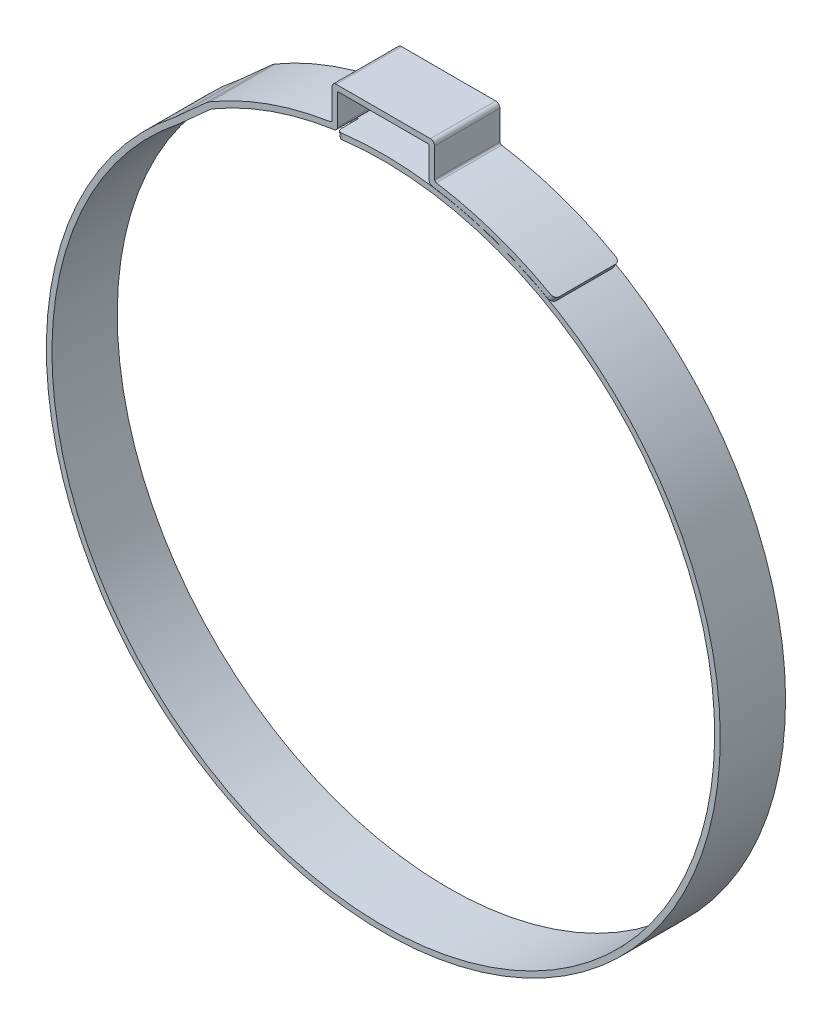
SolidWorks part; units mm, degrees
note: '?' marks a value the reader was unsure of.
material "Alloy Steel"
ref_plane "Front" through (0, 0, 0) normal (0, 0, 1) x (1, 0, 0)
ref_plane "Top" through (0, 0, 0) normal (0, 1, 0) x (1, 0, 0)
ref_plane "Right" through (0, 0, 0) normal (1, 0, 0) x (0, 0, -1)
sketch "Sketch1" plane through (0, 0, 0) normal (0, 0, 1) x (1, 0, 0)
  line L0 (0, 0) -> (0, 36.25) construction
  line L1 (0, 36.25) -> (0, 40.2945) construction
  line L2 (-5, 36.25) -> (5, 36.25) construction
  line L3 (-5, 36.5445) -> (-5, 40.2945) construction
  line L4 (-5, 40.2945) -> (5, 40.2945) construction
  line L5 (5, 40.2945) -> (5, 36.5445) construction
  line L6 (-36.25, 0) -> (0, 0) construction
  line L7 (0, 0) -> (36.25, 0) construction
  line L8 (-5.6096, 36.5445) -> (-5.6096, 40.9041)
  line L9 (-5, 36.5445) -> (-5.6096, 36.5445)
  line L10 (-5.6096, 40.9041) -> (5.6096, 40.9041)
  line L11 (5.6096, 40.9041) -> (5.6096, 36.5445)
  line L12 (5.6096, 36.5445) -> (5, 36.5445)
  line L13 (0, 40.2945) -> (0, 40.9041) construction
  line L14 (-5, 36.5445) -> (5, 36.5445)
  circle A0 centre (0, 0) radius 36.25 construction
  circle A1 centre (0, 0) radius 36.8596 construction
  circle A2 centre (0, 0) radius 36.885 construction
  dimension "D3" = 3.75
  dimension "D1" = 0.6096
extrude "Boss-Extrude1" add sketch "Sketch1" along normal mid plane 7.1437
sketch "Sketch4" plane through (0, 40.9041, 0) normal (0, 1, 0) x (1, 0, 0)
  line L0 (-1.9284, 0) -> (-3, 0) construction
  line L1 (0, -1.0716) -> (0, 1.0716) construction
  line L2 (-1.9284, 0) -> (1.9284, 0) construction
  line L3 (-36.25, 0) -> (36.25, 0) construction
  line L4 (-1.9284, 1.0716) -> (1.9284, 1.0716)
  line L5 (-1.9284, -1.0716) -> (1.9284, -1.0716)
  line L6 (1.9284, 0) -> (3, 0) construction
  arc A0 (-1.9284, 1.0716) -> (-1.9284, -1.0716) centre (-1.9284, 0) ccw
  arc A1 (1.9284, -1.0716) -> (1.9284, 1.0716) centre (1.9284, 0) ccw
  point P5 (0, 0)
  dimension "D2" = 2.1431
  dimension "D1" = 6
extrude "Cut-Extrude1" [suppressed] cut sketch "Sketch4" against normal blind 0.75
fillet "Fillet1" [suppressed] radius 0.4875
fillet "Fillet2" [suppressed] radius 0.1875
shell "Shell1" thickness 0.6096
sketch "Sketch5" plane through (0, 0, 0) normal (0, 0, 1) x (1, 0, 0)
  line L0 (18.4338, 31.9483) -> (0, 0) construction
  line L1 (5, 36.5445) -> (0, 0) construction
  arc A0 (5, 36.5445) -> (18.4338, 31.9483) centre (0, 0) cw
  dimension "Connector Strap Length" = 14.2875
extrude "Extrude-Thin3" add sketch "Sketch5" along normal mid plane 7.1437 thin thin type one direction reverse wall 0.6096
sketch "Sketch6" plane through (0, 0, 0) normal (0, 0, 1) x (1, 0, 0)
  line L0 (-18.8456, 31.7072) -> (0, 0) construction
  line L2 (-19.0354, 31.5362) -> (-22.3687, 28.5326)
  line L3 (-29.0363, 21.7015) -> (0, 0) construction
  line L4 (-22.4301, 28.4772) -> (0, 0) construction
  arc A0 (-5, 36.5445) -> (-18.6176, 31.8416) centre (0, 0) ccw
  arc A1 (-29.0363, 21.7015) -> (-5, 35.9035) centre (0, 0) ccw
  arc A2 (-22.3687, 28.5326) -> (-22.4929, 28.4277) centre (-24.0674, 30.4176) cw
  arc A3 (-18.6176, 31.8416) -> (-19.0354, 31.5362) centre (-17.3368, 29.6511) ccw
  arc A4 (-29.0363, 21.7015) -> (-22.4929, 28.4277) centre (0, 0) cw
  circle A5 centre (0, 0) radius 36.25 construction
  dimension "D4" = 2.5375
  dimension "D2" = 15
  dimension "D3" = 7.5
  dimension "D1" = 14.5
extrude "Extrude-Thin4" add sketch "Sketch6" along normal mid plane 7.1437 thin
sketch "Sketch7" plane through (0, 0, 0) normal (0, 0, 1) x (1, 0, 0)
  line L1 (-18.9253, 32.3679) -> (-18.6176, 31.8416)
  line L3 (-18.6176, 31.8416) -> (0, 0)
  line L4 (-35.6555, 9.3444) -> (-38.0388, 9.969)
  line L5 (-18.9253, 32.3679) -> (-19.8484, 33.9466)
  line L6 (0, 0) -> (-35.6555, 9.3444)
  arc A0 (-38.0388, 9.969) -> (-19.8484, 33.9466) centre (0, 0) cw
  arc A1 (-18.6176, 31.8416) -> (-19.0354, 31.5362) centre (-17.3368, 29.6511) ccw construction
  arc A2 (-5, 36.5445) -> (-18.6176, 31.8416) centre (0, 0) ccw construction
  arc A10 (-22.8711, 28.9058) -> (-5.0841, 36.5073) centre (0, 0) ccw construction
  dimension "D1" = 1.8288
  dimension "D2" = 45
extrude "Cut-Extrude2" [suppressed] cut sketch "Sketch7" against normal mid plane 2.432
sketch "Sketch8" [suppressed] plane through (0, 0, 0) normal (0, 0, 1) x (1, 0, 0)
  line L0 (-31.3283, 23.7669) -> (0, 0) construction
  line L1 (0, 0) -> (-35.0658, 9.1898) construction
  line L2 (0, 0) -> (-18.6176, 31.8416) construction
  line L3 (-29.3654, 22.2778) -> (-28.8798, 21.9094) construction
  line L4 (-24.4134, 27.4997) -> (0, 0) construction
  line L5 (-32.6967, 15.8784) -> (0, 0) construction
  arc A0 (-5, 36.5445) -> (-18.6176, 31.8416) centre (0, 0) ccw construction
  arc A1 (-5, 36.5445) -> (-18.6176, 31.8416) centre (0, 0) ccw construction
  arc A2 (-19.8484, 33.9466) -> (-38.0388, 9.969) centre (0, 0) ccw construction
  arc A3 (-35.0658, 9.1898) -> (-5, 35.9035) centre (0, 0) ccw construction
  circle A4 centre (0, 0) radius 36.8596 construction
  arc A5 (-22.4929, 28.4277) -> (-5, 35.9035) centre (0, 0) ccw construction
  circle A6 centre (0, 0) radius 36.25 construction
  arc A7 (-35.0658, 9.1898) -> (-32.6967, 15.8784) centre (5.7902, -1.5175) cw
  arc A8 (-32.6967, 15.8784) -> (-24.4134, 27.4997) centre (0.9059, 0.6902) cw
  arc A9 (-24.4134, 27.4997) -> (-18.6176, 31.8416) centre (-2.532, 4.3304) cw
  point P19 (-29.1226, 22.0936)
  dimension "D1" = 22.5
extrude "Extrude-Thin5" [suppressed] add sketch "Sketch8" along normal mid plane 2.3813 thin
sketch "Sketch12" [suppressed] plane through (0, 0, 0) normal (0, 0, 1) x (1, 0, 0)
  line L0 (-5.6453, -0.2315) -> (0, 0) construction
  line L1 (0, 0) -> (-4.5478, 4.1895) construction
  line L2 (-5.5488, 2.0363) -> (0, 0) construction
  arc A0 (-2.75, 5.5382) -> (-4.5478, 4.1895) centre (0, 0) ccw construction
  arc A1 (-2.75, 5.5382) -> (-4.5478, 4.1895) centre (0, 0) ccw construction
  arc A2 (-5.6453, -0.2315) -> (0, -5.65) centre (0, 0) ccw construction
  arc A3 (-5.6453, -0.2315) -> (-5.5488, 2.0363) centre (7.9561, 0.3262) cw
  arc A4 (-5.5488, 2.0363) -> (-4.5478, 4.1895) centre (-1.6784, 1.5462) cw
  dimension "D1" = 22.5
extrude "Extrude-Thin7" [suppressed] add sketch "Sketch12" along normal mid plane 2.3813 thin
sketch "Sketch9" plane through (0, 0, 0) normal (0, 0, 1) x (1, 0, 0)
  line L0 (0, 0) -> (-18.2971, 31.2934) construction
  line L4 (-18.9253, 32.3679) -> (-18.2971, 31.2934) construction
  arc A0 (-5, 35.9035) -> (-18.2971, 31.2934) centre (0, 0) ccw
  circle A1 centre (0, 0) radius 36.25 construction
extrude "Extrude-Thin6" add sketch "Sketch9" along normal mid plane 2.3813 thin
sketch "Sketch10" plane through (0, 0, 0) normal (0, 0, 1) x (1, 0, 0)
  line L0 (0, 0) -> (16.4971, 33.6703) construction
  line L1 (0, 0) -> (15.3474, 34.2097) construction
  line L2 (0, 0) -> (14.1801, 34.7098) construction
  line L3 (0, 0) -> (12.9965, 35.1701) construction
  line L4 (0, 0) -> (18.7385, 32.4764) construction
  line L5 (0, 0) -> (11.798, 35.59) construction
  line L6 (0, 0) -> (10.586, 35.9692) construction
  line L7 (10.586, 35.9692) -> (10.4067, 35.36)
  line L8 (11.798, 35.59) -> (11.5982, 34.9873)
  line L9 (12.9965, 35.1701) -> (12.7764, 34.5745)
  line L10 (14.1801, 34.7098) -> (13.94, 34.1219)
  line L11 (15.3474, 34.2097) -> (15.0875, 33.6303)
  line L12 (16.4971, 33.6703) -> (16.2178, 33.1001)
  arc A0 (18.7385, 32.4764) -> (5.6096, 37.0726) centre (0, 0) ccw construction
  arc A1 (10.586, 35.9692) -> (11.798, 35.59) centre (0, 0) cw
  circle A2 centre (0, 0) radius 36.8596 construction
  arc A3 (10.4067, 35.36) -> (11.5982, 34.9873) centre (0, 0) cw
  arc A4 (12.9965, 35.1701) -> (14.1801, 34.7098) centre (0, 0) cw
  arc A5 (15.3474, 34.2097) -> (16.4971, 33.6703) centre (0, 0) cw
  arc A6 (12.7764, 34.5745) -> (13.94, 34.1219) centre (0, 0) cw
  arc A7 (15.0875, 33.6303) -> (16.2178, 33.1001) centre (0, 0) cw
  dimension "D3" = 1.27
  dimension "D4" = 1.27
  dimension "D5" = 1.27
  dimension "D6" = 1.27
extrude "Cut-Extrude3" [suppressed] cut sketch "Sketch10" against normal mid plane 1.7859
fillet "Fillet4" radius 0.4572 4 edges at (5.6096, 40.9041, 0) (-5.6096, 40.9041, 0) (5, 36.5445, 0) (-5, 36.5445, 0)
fillet "Fillet5" radius 0.2286 2 edges at (5.6096, 37.0726, 0) (-5.6096, 37.0726, 0)
fillet "Fillet6" radius 0.1143 2 edges at (5, 40.2945, 0) (-5, 40.2945, 0)
fillet "Fillet7" radius 0.508 6 edges at (18.5862, 32.2124, -3.5719) (18.5862, 32.2124, 3.5719) (-5.042, 36.2054, -3.5719) (-5.042, 36.2054, 3.5719) (-18.4509, 31.5566, 1.1906) (-18.4509, 31.5566, -1.1906)
sketch "Sketch11" [suppressed] plane through (0, 0, 0) normal (0, 0, 1) x (1, 0, 0)
  line L0 (15.3474, 34.2097) -> (15.0875, 33.6303) construction
  line L2 (15.3474, 34.2097) -> (15.0979, 33.6535) construction
  line L3 (16.4971, 33.6703) -> (16.2178, 33.1001) construction
  line L4 (16.2289, 33.1229) -> (16.4971, 33.6703) construction
  line L5 (15.1107, 33.6199) -> (16.1395, 34.2086)
  line L6 (15.1107, 33.6199) -> (15.3706, 34.1993) construction
  line L8 (17.165, 33.7057) -> (17.0309, 33.432)
  line L9 (17.0309, 33.432) -> (0, 0) construction
  line L10 (12.8003, 34.5656) -> (13.4809, 34.9873)
  line L11 (14.2728, 34.8695) -> (13.9635, 34.1123)
  line L12 (11.8797, 35.7556) -> (11.0816, 35.8196)
  line L13 (11.8797, 35.7556) -> (11.6223, 34.9793)
  line L14 (11.6062, 35.0114) -> (11.798, 35.59) construction
  line L15 (13.9496, 34.1455) -> (14.1801, 34.7098) construction
  line L16 (10.4311, 35.3528) -> (10.6104, 35.962) construction
  line L17 (10.586, 35.9692) -> (10.4139, 35.3844) construction
  line L18 (12.8003, 34.5656) -> (13.0204, 35.1613) construction
  line L19 (12.9965, 35.1701) -> (12.7852, 34.5983) construction
  line L20 (11.0816, 35.8196) -> (10.4311, 35.3528)
  line L21 (13.4809, 34.9873) -> (14.2728, 34.8695)
  line L22 (16.4855, 33.7043) -> (16.1949, 33.1112) construction
  line L23 (16.4855, 33.7043) -> (15.79, 33.3063)
  arc A0 (16.4855, 33.7043) -> (17.0309, 33.432) centre (0, 0) cw
  arc A1 (-22.8711, 28.9058) -> (-4.5805, 36.5739) centre (0, 0) ccw construction
  arc A2 (16.1395, 34.2086) -> (17.165, 33.7057) centre (0, 0) cw
  arc A3 (15.1107, 33.6199) -> (15.79, 33.3063) centre (0, 0) cw
  arc A5 (18.2968, 32.7273) -> (5.8028, 37.0428) centre (0, 0) ccw construction
  arc A6 (12.8003, 34.5656) -> (13.9635, 34.1123) centre (0, 0) cw
  arc A7 (10.4311, 35.3528) -> (11.6223, 34.9793) centre (0, 0) cw
  point P24 (11.8222, 35.582)
  point P41 (14.2036, 34.7002)
  dimension "D2" = 0.0254
  dimension "D5" = 0.6096
  dimension "D7" = 0.0254
  dimension "D8" = 0.0254
  dimension "D9" = 0.0254
  dimension "D10" = 0.0254
  dimension "D11" = 0.1829
  dimension "D12" = 0.1829
  dimension "D3" = 0.0254
  dimension "D6" = 0.6096
  dimension "D13" = 0.3048
extrude "Boss-Extrude2" [suppressed] add sketch "Sketch11" along normal mid plane 1.6589
sketch "Ref" plane through (0, 0, 0) normal (0, 0, 1) x (1, 0, 0)
  line L1 (5.1524, 40.9041) -> (-5.1524, 40.9041) construction
  line L2 (5.6096, 40.9041) -> (-5.6096, 40.9041)
  line L4 (4.8857, 40.2945) -> (-4.8857, 40.2945) construction
  line L7 (5.6096, 40.2945) -> (-5.6096, 40.2945)
  line L8 (-5.6096, 40.4469) -> (-5.6096, 37.2687) construction
  line L9 (5.6096, 37.2687) -> (5.6096, 40.4469) construction
ref_axis "Center Axis 1" through (0, 0, -3.9606) along (0, 0, 1)?
equation "\"D3@Sketch1\" = \"Ear Width (Inside)@Sketch1\" * .375"
equation "\"D2@Sketch4\" = \"Band Wd@Boss-Extrude1\" * .3"
equation "\"D1@Sketch4\" = \"Ear Width (Inside)@Sketch1\" * .6"
equation "\"D1@Cut-Extrude1\" = \"D3@Sketch1\" * .2"
equation "\"D1@Shell1\" = \"Band Thickness@Sketch1\""
equation "\"D5@Extrude-Thin3\" = \"Band Thickness@Sketch1\""
equation "\"D1@Extrude-Thin3\" = \"Band Wd@Boss-Extrude1\""
equation "\"D5@Extrude-Thin4\" = \"Band Thickness@Sketch1\""
equation "\"D1@Extrude-Thin4\" = \"Band Wd@Boss-Extrude1\""
equation "\"D1@Fillet4\" = \"Band Thickness@Sketch1\" * .75"
equation "\"D1@Fillet5\" = \"D1@Fillet4\" * .5"
equation "\"D1@Fillet6\" = \"D1@Fillet4\" * .25"
equation "\"D1@Fillet1\" = \"D1@Cut-Extrude1\" * .65"
equation "\"D1@Fillet2\" = \"D1@Cut-Extrude1\" * .25"
equation "\"D1@Sketch1\" = \"Band Thickness@Sketch1\""
equation "\"D1@Cut-Extrude2\" = ( \"Band Wd@Boss-Extrude1\" / 3 ) + .002"
equation "\"D1@Extrude-Thin5\" = \"Band Wd@Boss-Extrude1\" / 3"
equation "\"D5@Extrude-Thin5\" = \"Band Thickness@Sketch1\""
equation "\"D1@Extrude-Thin6\" = \"D1@Extrude-Thin5\""
equation "\"D5@Extrude-Thin6\" = \"Band Thickness@Sketch1\""
equation "\"D1@Cut-Extrude3\" = \"Band Wd@Boss-Extrude1\" * .25"
equation "\"D11@Sketch11\" = \"Band Thickness@Sketch1\" * .3"
equation "\"D12@Sketch11\" = \"D11@Sketch11\""
equation "\"D1@Boss-Extrude2\" = \"D1@Cut-Extrude3\" - .005"
equation "\"D4@Sketch6\" = \"Clamp ID@Sketch1\" * .035"
equation "\"D1@Sketch7\" = \"Band Thickness@Sketch1\" * 3"
equation "\"D3@Sketch10\" = \"D2@Sketch10\""
equation "\"D4@Sketch10\" = \"D3@Sketch10\""
equation "\"D5@Sketch10\" = \"D2@Sketch10\""
equation "\"D6@Sketch10\" = \"D2@Sketch10\""
equation "\"D5@Sketch11\" = \"Band Thickness@Sketch1\""
equation "\"D6@Sketch11\" = \"Band Thickness@Sketch1\""
equation "\"D13@Sketch11\" = \"Band Thickness@Sketch1\" / 2"
equation "\"D1@Sketch6\" = \"Clamp ID@Sketch1\" * .2"
equation "\"D1@Extrude-Thin7\" = \"Band Wd@Boss-Extrude1\" / 3"
equation "\"D5@Extrude-Thin7\" = \"Band Thickness@Sketch1\""
